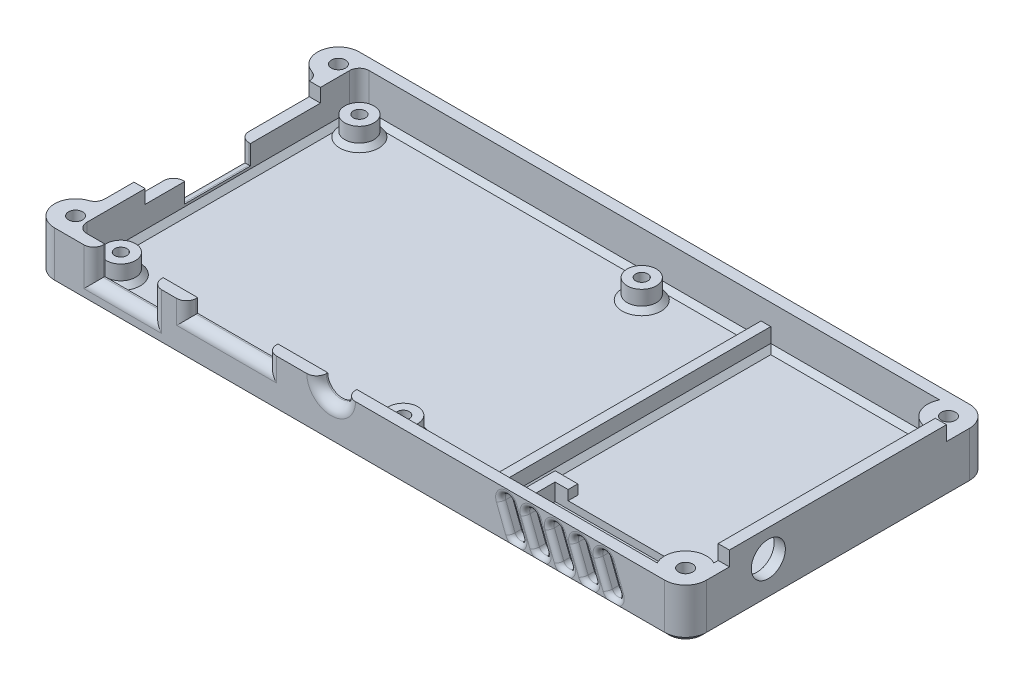
SolidWorks part; units mm, degrees
ref_plane "Front Plane" through (0, 0, 0) normal (0, 0, 1) x (1, 0, 0)
ref_plane "Top Plane" through (0, 0, 0) normal (0, 1, 0) x (1, 0, 0)
ref_plane "Right Plane" through (0, 0, 0) normal (1, 0, 0) x (0, 0, -1)
sketch "Sketch1" plane through (0, 0, 0) normal (0, 1, 0) x (1, 0, 0)
  line L0 (-71.5618, 3.106) -> (51.4382, 3.106) construction
  line L1 (-71.5618, 31.106) -> (51.4382, 31.106)
  line L2 (-71.5618, 31.106) -> (-71.5618, -24.894)
  line L3 (-71.5618, -24.894) -> (51.4382, -24.894)
  line L4 (51.4382, 31.106) -> (51.4382, -24.894)
  line L5 (-60.6618, -24.894) -> (-60.6618, -31.6828) construction
  line L6 (-68.0618, 27.606) -> (-10.0618, 27.606)
  line L7 (-68.0618, 27.606) -> (-68.0618, -21.394)
  line L8 (-68.0618, -21.394) -> (-10.0618, -21.394)
  line L9 (-10.0618, 27.606) -> (-10.0618, -21.394)
  line L10 (-39.5618, -24.894) -> (-39.5618, -31.6828) construction
  line L11 (-18.0618, -24.894) -> (-18.0618, -31.6828) construction
  line L12 (-65.4118, -26.5648) -> (-55.9118, -26.5648) construction
  line L13 (-48.0618, -26.5648) -> (-31.0618, -26.5648) construction
  line L14 (-22.0618, -26.5648) -> (-14.0618, -26.5648) construction
  line L15 (-72.5618, 9.606) -> (-72.5618, -3.394) construction
  line L16 (-71.5618, 3.106) -> (-72.5618, 3.106) construction
  dimension "D1" = 123
  dimension "D2" = 56
  dimension "D3" = 49
  dimension "D4" = 58
  dimension "D5" = 3.5
  dimension "D6" = 3.5
  dimension "D7" = 10.9
  dimension "D8" = 32
  dimension "D9" = 53.5
  dimension "D10" = 2
  dimension "D11" = 13
  dimension "D12" = 9.5
  dimension "D13" = 17
  dimension "D14" = 8
sketch "Sketch3" plane through (0, 0, 0) normal (0, 1, 0) x (1, 0, 0)
  line L4 (54.7382, 34.406) -> (-74.8618, 34.406)
  line L5 (-74.8618, 34.406) -> (-74.8618, -28.194)
  line L6 (-74.8618, -28.194) -> (54.7382, -28.194)
  line L7 (54.7382, -28.194) -> (54.7382, 34.406)
  line L8 (52.4382, 32.106) -> (-72.5618, 32.106)
  line L9 (52.4382, -25.894) -> (52.4382, 32.106)
  line L10 (-72.5618, -25.894) -> (52.4382, -25.894)
  line L11 (-72.5618, 32.106) -> (-72.5618, -25.894)
  line L12 (52.4382, 32.106) -> (-72.5618, 32.106)
  line L13 (52.4382, -25.894) -> (52.4382, 32.106)
  line L14 (-72.5618, -25.894) -> (52.4382, -25.894)
  line L15 (-72.5618, 32.106) -> (-72.5618, -25.894)
  line L16 (-10.0618, 3.106) -> (-10.0618, 34.406) construction
  line L17 (-71.5618, 3.106) -> (51.4382, 3.106) construction
  line L20 (-74.8618, 3.106) -> (52.7382, 3.106) construction
  line L25 (54.7382, -28.194) -> (54.7382, 34.406) construction
  line L26 (52.4382, -25.894) -> (52.4382, 32.106) construction
  dimension "D1" = 1
  dimension "D2" = 2.3
extrude "Boss-Extrude1" add sketch "Sketch3" along normal blind 10.3
sketch "Sketch5" plane through (0, 0, 0) normal (0, 1, 0) x (1, 0, 0)
  line L1 (-72.5618, 32.106) -> (52.4382, 32.106)
  line L2 (-72.5618, 32.106) -> (-72.5618, -25.894)
  line L3 (-72.5618, -25.894) -> (52.4382, -25.894)
  line L4 (52.4382, 32.106) -> (52.4382, -25.894)
extrude "Boss-Extrude2" add sketch "Sketch5" along normal blind 2
sketch "Sketch6" plane through (0, 2, 0) normal (0, 1, 0) x (1, 0, 0)
  circle A0 centre (-68.0618, 27.606) radius 3
  circle A1 centre (-68.0618, -21.394) radius 3
  circle A2 centre (-10.0618, -21.394) radius 3
  circle A3 centre (-10.0618, 27.606) radius 3
extrude "Boss-Extrude3" add sketch "Sketch6" along normal blind 4
hole_wizard "Ø2.5 (2.5) Diameter Hole1" positions "Sketch8" profile "Sketch9" hole size "Ø2.5" standard "ANSI Metric"
sketch "Sketch8" plane through (0, 6, 0) normal (0, 1, 0) x (1, 0, 0)
  point P0 (-68.0618, 27.606)
  point P3 (-10.0618, 27.606)
  point P6 (-10.0618, -21.394)
  point P9 (-68.0618, -21.394)
sketch "Sketch9" plane through (-68.0618, 6, -27.606) normal (1, 0, 0) x (0, 0, 1)
  line L0 (0, 0) -> (0, 8.7511)
  line L1 (0, 8.7511) -> (1.25, 8)
  line L2 (1.25, 8) -> (1.25, 0)
  line L5 (1.25, 0) -> (0, 0)
  line L10 (0, 8.7511) -> (-1.25, 8) construction
  line L11 (0, -6.35) -> (0, 107.95) construction
  dimension "Hole Dia." = 2.5
  dimension "Hole Depth" = 8
  dimension "Drill Angle" = 118
sketch "Sketch10" plane through (0, 2, 0) normal (0, 1, 0) x (1, 0, 0)
  line L0 (52.4382, 32.106) -> (-72.5618, 32.106) construction
  line L1 (9.9382, 32.106) -> (11.9382, 32.106)
  line L2 (9.9382, 32.106) -> (9.9382, -25.894)
  line L3 (9.9382, -25.894) -> (11.9382, -25.894)
  line L4 (11.9382, 32.106) -> (11.9382, -25.894)
  line L5 (-72.5618, -25.894) -> (52.4382, -25.894) construction
  line L6 (-10.0618, 27.606) -> (-10.0618, -21.394) construction
  dimension "D1" = 2
  dimension "D2" = 20
extrude "Boss-Extrude4" add sketch "Sketch10" along normal blind 4
sketch "Sketch11" plane through (0, 0, 28.194) normal (0, 0, 1) x (1, 0, 0)
  line L0 (-74.8618, 10.3) -> (-74.8618, 0) construction
  line L1 (-66.8618, 10.3) -> (-54.8618, 10.3)
  line L2 (-66.8618, 10.3) -> (-66.8618, 4.5)
  line L3 (-66.8618, 4.5) -> (-54.8618, 4.5)
  line L4 (-54.8618, 10.3) -> (-54.8618, 4.5)
  line L5 (-74.8618, 0) -> (54.7382, 0) construction
  line L6 (-60.8618, 10.3) -> (-60.6618, 0) construction
  line L7 (-65.4118, 0) -> (-55.9118, 0) construction
  line L9 (-47.778, 10.3) -> (-31.278, 10.3)
  line L10 (-47.778, 10.3) -> (-47.778, 7.5)
  line L11 (-47.778, 7.5) -> (-31.278, 7.5)
  line L12 (-31.278, 10.3) -> (-31.278, 7.5)
  line L13 (-68.0618, 0) -> (-10.0618, 0) construction
  line L14 (-39.5618, 0) -> (-39.528, 10.3) construction
  line L15 (-48.0618, 0) -> (-31.0618, 0) construction
  line L16 (-18.0618, 0) -> (-18.0618, 10.3) construction
  line L17 (-22.0618, 0) -> (-14.0618, 0) construction
  line L18 (-74.8618, 10.3) -> (54.7382, 10.3) construction
  circle A0 centre (-18.0618, 10.3) radius 3
  dimension "D5" = 6
  dimension "D1" = 4.5
  dimension "D2" = 12
  dimension "D3" = 7.5
  dimension "D4" = 16.5
  dimension "D6" = 8
extrude "Cut-Extrude1" cut sketch "Sketch11" against normal up to next
sketch "Sketch12" plane through (-74.8618, 0, 0) normal (-1, 0, 0) x (0, 0, 1)
  line L0 (-3.106, 0) -> (-3.106, 10.3) construction
  line L1 (-27.606, 0) -> (21.394, 0) construction
  line L2 (-34.406, 10.3) -> (28.194, 10.3) construction
  line L4 (-9.7329, 10.3) -> (3.7671, 10.3)
  line L5 (-9.7329, 10.3) -> (-9.7329, 3.5)
  line L6 (-9.7329, 3.5) -> (3.7671, 3.5)
  line L7 (3.7671, 10.3) -> (3.7671, 3.5)
  line L8 (-24.106, 10.3) -> (11.894, 10.3)
  line L9 (-24.106, 10.3) -> (-24.106, 7.5)
  line L10 (-24.106, 7.5) -> (11.894, 7.5)
  line L11 (11.894, 10.3) -> (11.894, 7.5)
  dimension "D1" = 13.5
  dimension "D2" = 3.5
  dimension "D3" = 7.5
  dimension "D4" = 36
extrude "Cut-Extrude2" cut sketch "Sketch12" against normal up to next contours L10 L11 L8 L9 | L7 L6 L5 L4
fillet "Fillet6" radius 2 1 edges at (52.4382, 6.15, -32.106)
fillet "Fillet8" radius 2 2 edges at (-72.5618, 6.15, 25.894) (-72.5618, 6.15, -32.106)
chamfer "Chamfer1" distance 1 angle 45 4 edges at (-68.0618, 2, 24.394) (-10.0618, 2, 24.394) (-10.0618, 2, -24.606) (-68.0618, 2, -24.606)
fillet "Fillet9" radius 2 9 edges at (-74.8618, 5.5, -9.7329) (-74.8618, 3.5, -2.9829) (-74.8618, 5.5, 3.7671) (-18.0618, 7.3, 28.194) (-31.278, 8.9, 28.194) (-47.778, 8.9, 28.194) (-39.528, 7.5, 28.194) (-54.8618, 7.4, 28.194) (-60.8618, 4.5, 28.194)
sketch "Sketch13" plane through (54.7382, 0, -61.1442) normal (1, 0, 0) x (0, 0, -1)
  line L0 (-89.3382, 10.3) -> (-89.3382, 0) construction
  circle A0 centre (-72.3382, 7.7223) radius 3.5
  dimension "D1" = 17
sketch "Sketch17" plane through (0, 0, 0) normal (0, 1, 0) x (1, 0, 0)
  line L0 (-74.8618, 34.406) -> (-74.8618, 24.106) construction
  line L1 (-74.8618, 34.406) -> (-74.8618, 25.806)
  line L2 (-74.8618, 25.806) -> (-74.659, 25.9406)
  line L3 (-74.8618, -19.594) -> (-74.8618, -28.194)
  line L4 (-74.8618, -28.194) -> (-74.659, -28.0594)
  arc A0 (-74.8618, -19.594) -> (-74.8618, -28.194) centre (-74.8618, -23.894) ccw
  arc A1 (-74.8618, 34.406) -> (-74.8618, 25.806) centre (-74.8618, 30.106) ccw
extrude "Boss-Extrude6" add sketch "Sketch17" along normal up to vertex (10.3 mm away) contours L1 A1 | L3 A0 region at (-76.6867, 0, -30.106) region at (-76.6867, 0, 23.894) up to point (-74.8618, 10.3, 28.194)
hole_wizard "Ø2.9 (2.9) Diameter Hole2" positions "Sketch19" profile "Sketch18" hole size "Ø2.9" standard "ANSI Metric" end condition up to next
sketch "Sketch19" plane through (0, 10.3, 0) normal (0, 1, 0) x (1, 0, 0)
  point P0 (-74.8618, 30.106)
sketch "Sketch18" plane through (-74.8618, 10.3, -30.106) normal (1, 0, 0) x (0, 0, 1)
  line L0 (0, 0) -> (0, 10.3)
  line L1 (0, 10.3) -> (1.45, 10.3)
  line L2 (1.45, 10.3) -> (1.45, 0)
  line L5 (1.45, 0) -> (0, 0)
  line L11 (0, -6.35) -> (0, 107.95) construction
  dimension "Thru Hole Dia." = 2.9
  dimension "Thru Hole Depth" = 10.3
hole_wizard "Ø2.9 (2.9) Diameter Hole1" positions "Sketch21" profile "Sketch20" hole size "Ø2.9" standard "ANSI Metric" end condition up to next
sketch "Sketch21" plane through (0, 10.3, 0) normal (0, 1, 0) x (1, 0, 0)
  point P0 (-74.8618, -23.894)
sketch "Sketch20" plane through (-74.8618, 10.3, 23.894) normal (1, 0, 0) x (0, 0, 1)
  line L0 (0, 0) -> (0, 10.3)
  line L1 (0, 10.3) -> (1.45, 10.3)
  line L2 (1.45, 10.3) -> (1.45, 0)
  line L5 (1.45, 0) -> (0, 0)
  line L11 (0, -6.35) -> (0, 107.95) construction
  dimension "Thru Hole Dia." = 2.9
  dimension "Thru Hole Depth" = 10.3
sketch "Sketch24" plane through (0, 2, 0) normal (0, 1, 0) x (1, 0, 0)
  line L0 (11.9382, 3.106) -> (61.5789, 3.106) construction
  line L1 (11.9382, -25.894) -> (11.9382, 32.106) construction
  line L2 (54.7382, -28.194) -> (54.7382, 34.406) construction
  circle A0 centre (50.4382, -23.894) radius 4.3
  circle A1 centre (50.4382, 30.106) radius 4.3
  dimension "D1" = 4.3
extrude "Boss-Extrude7" add sketch "Sketch24" along normal up to surface (8.3 mm away) up to face at (-74.8618, 10.3, 25.344)
hole_wizard "Ø2.9 (2.9) Diameter Hole5" positions "Sketch31" profile "Sketch30" hole size "Ø2.9" standard "ANSI Metric" end condition up to next
sketch "Sketch31" plane through (0, 10.3, 0) normal (0, 1, 0) x (1, 0, 0)
  point P0 (50.4382, -23.894)
sketch "Sketch30" plane through (50.4382, 10.3, 23.894) normal (1, 0, 0) x (0, 0, 1)
  line L0 (0, 0) -> (0, 10.3)
  line L1 (0, 10.3) -> (1.45, 10.3)
  line L2 (1.45, 10.3) -> (1.45, 0)
  line L5 (1.45, 0) -> (0, 0)
  line L11 (0, -6.35) -> (0, 107.95) construction
  dimension "Thru Hole Dia." = 2.9
  dimension "Thru Hole Depth" = 10.3
hole_wizard "Ø2.9 (2.9) Diameter Hole4" positions "Sketch28" profile "Sketch27" hole size "Ø2.9" standard "ANSI Metric" end condition up to next
sketch "Sketch28" plane through (0, 10.3, 0) normal (0, 1, 0) x (1, 0, 0)
  point P0 (50.4382, 30.106)
sketch "Sketch27" plane through (50.4382, 10.3, -30.106) normal (1, 0, 0) x (0, 0, 1)
  line L0 (0, 0) -> (0, 10.3)
  line L1 (0, 10.3) -> (1.45, 10.3)
  line L2 (1.45, 10.3) -> (1.45, 0)
  line L5 (1.45, 0) -> (0, 0)
  line L11 (0, -6.35) -> (0, 107.95) construction
  dimension "Thru Hole Dia." = 2.9
  dimension "Thru Hole Depth" = 10.3
fillet "Fillet10" radius 4.3 1 edges at (54.7382, 5.15, -34.406)
fillet "Fillet18" radius 2 2 edges at (-74.8618, 5.15, 19.594) (-74.8618, 5.15, -25.806)
chamfer "Chamfer3" distance 1 angle 45 9 edges at (53.4788, 0, -33.1466) (-12.2118, 0, -34.406) (54.7382, 0, -0.956) (-79.1058, 0, -30.7975) (-75.2385, 0, -25.3002) (-74.8618, 0, -3.106) (-75.2385, 0, 19.0883) (-79.1058, 0, 24.5855) (-10.0618, 0, 28.194)
fillet "Fillet19" radius 2 1 edges at (-66.8618, 6.4, 28.194)
fillet "Fillet20" radius 4.3 1 edges at (54.7382, 5.65, 28.194)
chamfer "Chamfer5" distance 1 angle 45 8 edges at (-72.5618, 2, -3.106) (-71.976, 2, 25.3082) (-71.976, 2, -31.5202) (-30.3118, 2, 25.894) (-30.3118, 2, -32.106) (9.9382, 2, -3.106) (11.9382, 2, -3.106) (29.2849, 2, -32.106)
chamfer "Chamfer6" distance 1 angle 45 1 edges at (52.4382, 2, -3.106)
sketch "Sketch29" plane through (0, 10.3, 0) normal (0, 1, 0) x (1, 0, 0)
  line L0 (52.4382, -20.0874) -> (52.4382, 26.2994) construction
  line L1 (52.4382, 25.406) -> (54.7382, 25.406)
  line L2 (52.4382, 25.406) -> (52.4382, -19.194)
  line L3 (52.4382, -19.194) -> (54.7382, -19.194)
  line L4 (54.7382, 25.406) -> (54.7382, -19.194)
  line L5 (54.7382, -23.894) -> (54.7382, 30.106) construction
  line L6 (50.4382, 34.406) -> (-74.8618, 34.406) construction
  line L7 (-13.0618, -28.194) -> (50.4382, -28.194) construction
  dimension "D1" = 9
  dimension "D2" = 9
extrude "Boss-Extrude8" add sketch "Sketch29" along normal blind 3
extrude "Cut-Extrude3" cut sketch "Sketch13" against normal up to next
sketch "Sketch32" plane through (0, 2, 0) normal (0, 1, 0) x (1, 0, 0)
  line L0 (12.9382, -25.894) -> (46.6317, -25.894) construction
  line L1 (15.4382, -15.694) -> (45.5382, -15.694)
  line L2 (15.4382, -15.694) -> (15.4382, -25.894)
  line L3 (15.4382, -25.894) -> (45.5382, -25.894)
  line L4 (45.5382, -15.694) -> (45.5382, -25.894)
  line L5 (-72.5618, -23.894) -> (-72.5618, 30.106) construction
  dimension "D1" = 10.2
  dimension "D2" = 30.1
  dimension "D3" = 88
extrude "Cut-Extrude4" cut sketch "Sketch32" against normal blind 1.5
sketch "Sketch33" plane through (0, 2, 0) normal (0, 1, 0) x (1, 0, 0)
  line L0 (15.4382, -15.694) -> (15.4382, -25.894)
  line L2 (15.4382, -25.894) -> (13.4382, -25.894)
  line L3 (12.9382, -25.894) -> (15.4382, -25.894) construction
  line L4 (47.5382, -13.694) -> (47.5382, -20.8822)
  line L5 (47.5382, -20.8822) -> (45.5382, -20.8822)
  line L6 (45.5382, -25.894) -> (45.5382, -20.7012) construction
  line L7 (45.5382, -20.8822) -> (45.5382, -15.694)
  line L8 (30.4882, -15.694) -> (30.4882, -23.4127) construction
  line L9 (45.5382, -15.694) -> (15.4382, -15.694) construction
  line L10 (18.1083, -13.694) -> (18.1083, -15.694)
  line L11 (42.8681, -13.694) -> (42.8681, -15.694)
  line L12 (13.4382, -13.694) -> (13.4382, -27.894)
  line L13 (13.4382, -27.894) -> (47.5382, -27.894)
  line L14 (47.5382, -27.894) -> (47.5382, -13.694)
  line L15 (47.5382, -13.694) -> (13.4382, -13.694)
  line L16 (13.4382, -13.694) -> (13.4382, -25.894)
  line L17 (45.5382, -15.694) -> (42.8681, -15.694)
  line L19 (47.5382, -13.694) -> (42.8681, -13.694)
  line L20 (18.1083, -13.694) -> (13.4382, -13.694)
  line L21 (18.1083, -15.694) -> (15.4382, -15.694)
  dimension "D1" = 2
extrude "Boss-Extrude9" add sketch "Sketch33" along normal blind 2
sketch "Sketch34" plane through (0, 0, 28.194) normal (0, 0, 1) x (1, 0, 0)
  line L0 (17.9748, 7.7443) -> (19.8911, 2.8029) construction
  line L1 (19.1402, 8.1963) -> (21.0565, 3.2549)
  line L2 (16.8093, 7.2924) -> (18.7256, 2.3509)
  line L3 (22.9748, 7.7443) -> (24.8911, 2.8029) construction
  line L4 (24.1402, 8.1963) -> (26.0565, 3.2549)
  line L5 (21.8093, 7.2924) -> (23.7256, 2.3509)
  line L6 (27.9748, 7.7443) -> (29.8911, 2.8029) construction
  line L7 (29.1402, 8.1963) -> (31.0565, 3.2549)
  line L8 (26.8093, 7.2924) -> (28.7256, 2.3509)
  line L9 (32.9748, 7.7443) -> (34.8911, 2.8029) construction
  line L10 (34.1402, 8.1963) -> (36.0565, 3.2549)
  line L11 (31.8093, 7.2924) -> (33.7256, 2.3509)
  line L12 (37.9748, 7.7443) -> (39.8911, 2.8029) construction
  line L13 (39.1402, 8.1963) -> (41.0565, 3.2549)
  line L14 (36.8093, 7.2924) -> (38.7256, 2.3509)
  arc A0 (19.1402, 8.1963) -> (16.8093, 7.2924) centre (17.9748, 7.7443) ccw
  arc A1 (18.7256, 2.3509) -> (21.0565, 3.2549) centre (19.8911, 2.8029) ccw
  arc A2 (24.1402, 8.1963) -> (21.8093, 7.2924) centre (22.9748, 7.7443) ccw
  arc A3 (23.7256, 2.3509) -> (26.0565, 3.2549) centre (24.8911, 2.8029) ccw
  arc A4 (29.1402, 8.1963) -> (26.8093, 7.2924) centre (27.9748, 7.7443) ccw
  arc A5 (28.7256, 2.3509) -> (31.0565, 3.2549) centre (29.8911, 2.8029) ccw
  arc A6 (34.1402, 8.1963) -> (31.8093, 7.2924) centre (32.9748, 7.7443) ccw
  arc A7 (33.7256, 2.3509) -> (36.0565, 3.2549) centre (34.8911, 2.8029) ccw
  arc A8 (39.1402, 8.1963) -> (36.8093, 7.2924) centre (37.9748, 7.7443) ccw
  arc A9 (38.7256, 2.3509) -> (41.0565, 3.2549) centre (39.8911, 2.8029) ccw
  point P2 (18.9329, 5.2736)
  point P9 (23.9329, 5.2736)
  point P16 (28.9329, 5.2736)
  point P23 (33.9329, 5.2736)
  point P30 (38.9329, 5.2736)
extrude "Cut-Extrude5" cut sketch "Sketch34" against normal up to next
fillet "Fillet21" radius 1 20 edges at (37.5228, 8.9098, 28.194) (40.0983, 5.7256, 28.194) (40.343, 1.6375, 28.194) (32.5228, 8.9098, 28.194) (35.0983, 5.7256, 28.194) (35.343, 1.6375, 28.194) (27.5228, 8.9098, 28.194) (30.0983, 5.7256, 28.194) (30.343, 1.6375, 28.194) (22.5228, 8.9098, 28.194) (25.0983, 5.7256, 28.194) (25.343, 1.6375, 28.194) (17.5228, 8.9098, 28.194) (20.0983, 5.7256, 28.194) (20.343, 1.6375, 28.194) (37.7675, 4.8217, 28.194) (32.7675, 4.8217, 28.194) (27.7675, 4.8217, 28.194) (22.7675, 4.8217, 28.194) (17.7675, 4.8217, 28.194)
chamfer "Chamfer7" distance 1 angle 45 1 edges at (53.4788, 0, 26.9346)
